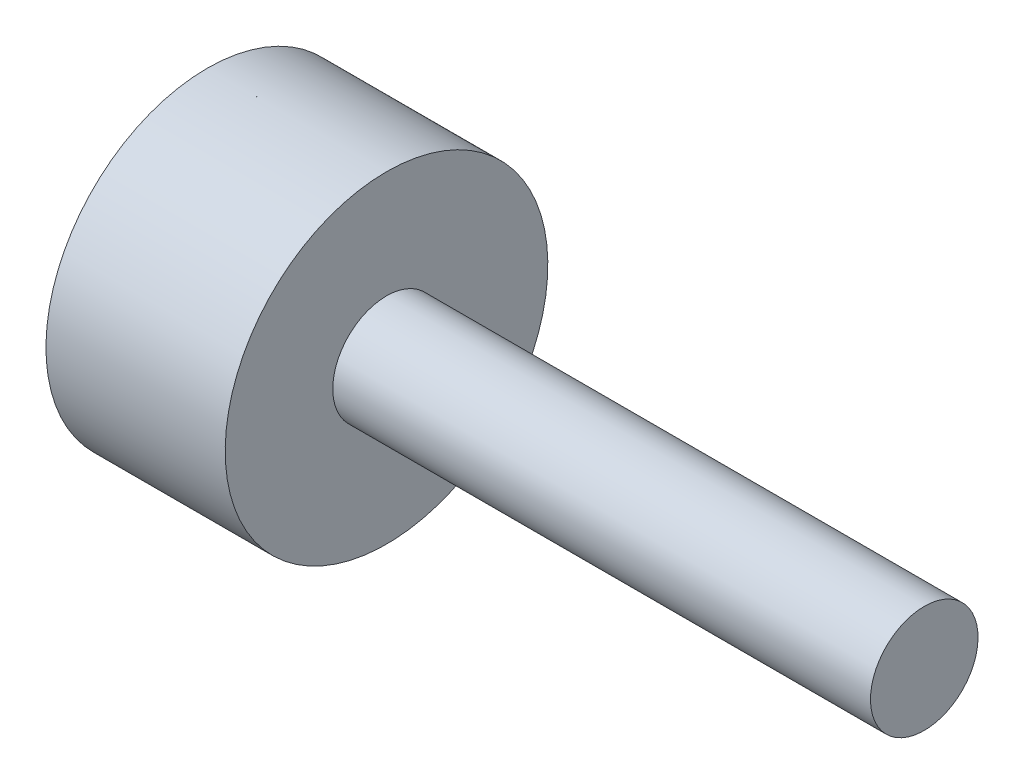
SolidWorks part; units mm, degrees
ref_plane "Front Plane" through (0, 0, 0) normal (0, 0, 1) x (1, 0, 0)
ref_plane "Top Plane" through (0, 0, 0) normal (0, 1, 0) x (1, 0, 0)
ref_plane "Right Plane" through (0, 0, 0) normal (1, 0, 0) x (0, 0, -1)
sketch "Sketch1" plane through (0, 0, 0) normal (0, 0, 1) x (1, 0, 0)
  line L0 (0, 0) -> (20, 0) construction
  line L1 (0, 0) -> (0, 4.5)
  line L2 (0, 4.5) -> (5, 4.5)
  line L3 (5, 4.5) -> (5, 1.5)
  line L4 (5, 1.5) -> (20, 1.5)
  line L5 (20, 1.5) -> (20, 0)
  line L6 (20, 0) -> (0, 0)
revolve "Revolve1" add sketch "Sketch1" angle 360 about L0
